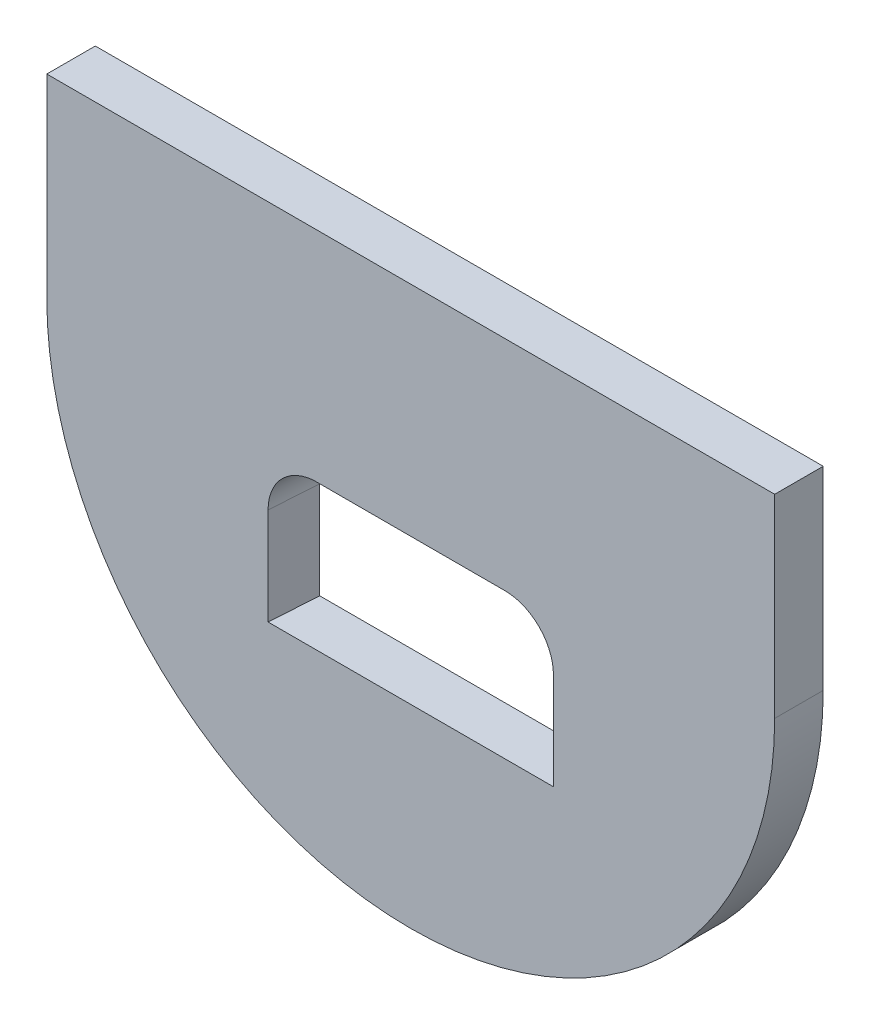
SolidWorks part; units mm, degrees
ref_plane "Front Plane" through (0, 0, 0) normal (0, 0, 1) x (1, 0, 0)
ref_plane "Top Plane" through (0, 0, 0) normal (0, 1, 0) x (1, 0, 0)
ref_plane "Right Plane" through (0, 0, 0) normal (1, 0, 0) x (0, 0, -1)
sketch "Sketch1" plane through (0, 0, 0) normal (0, 0, 1) x (1, 0, 0)
  line L0 (0, -40) -> (0, 0)
  line L1 (0, 0) -> (-150, 0)
  line L2 (-150, 0) -> (-150, -40)
  line L4 (-103.75, -45) -> (-46.25, -45)
  line L5 (-103.75, -45) -> (-103.75, -75)
  line L6 (-103.75, -75) -> (-46.25, -75)
  line L7 (-46.25, -45) -> (-46.25, -75)
  arc A0 (0, -40) -> (-150, -40) centre (-75, -40) cw
  point P6 (-75, -45)
  point P11 (-75, 0)
  dimension "D1" = 75
  dimension "D2" = 40
  dimension "D3" = 57.5
  dimension "D4" = 30
  dimension "D5" = 45
extrude "Boss-Extrude1" add sketch "Sketch1" along normal blind 10
chamfer "Chamfer1" distance 10 angle 3.71 2 edges at (-46.25, -60, 10) (-103.75, -60, 10)
fillet "Fillet1" radius 10 2 edges at (-104.0742, -45, 5) (-45.9258, -45, 5)
